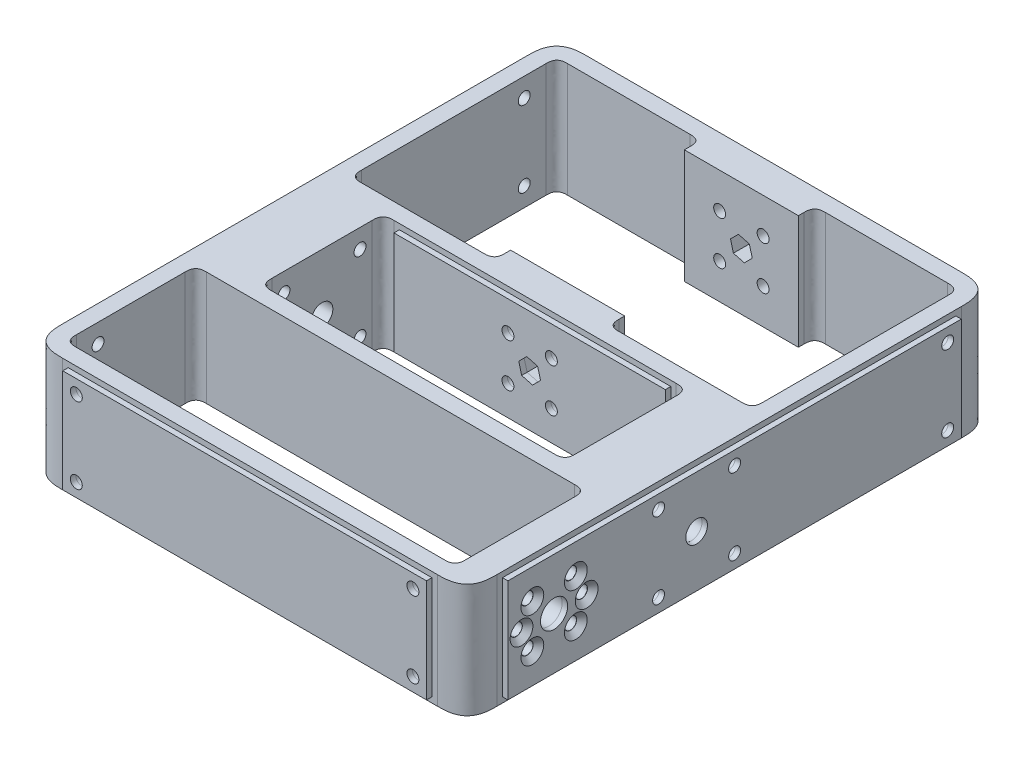
SolidWorks part; units mm, degrees
ref_plane "Front Plane" through (0, 0, 0) normal (0, 0, 1) x (1, 0, 0)
ref_plane "Top Plane" through (0, 0, 0) normal (0, 1, 0) x (1, 0, 0)
ref_plane "Right Plane" through (0, 0, 0) normal (1, 0, 0) x (0, 0, -1)
sketch "Sketch1" plane through (0, 0, 0) normal (0, 1, 0) x (1, 0, 0)
  line L0 (-93.2979, 0) -> (107.2162, 0) construction
  line L1 (-93.2979, -52.5) -> (97.3404, -52.5) construction
  line L2 (-74, -76.5) -> (74, -76.5)
  line L3 (-80, 110.5) -> (80, 110.5)
  line L4 (-80, 110.5) -> (-80, -82.5)
  line L5 (-80, -82.5) -> (80, -82.5)
  line L6 (80, 110.5) -> (80, -82.5)
  line L7 (74, -76.5) -> (74, -28.5)
  line L8 (74, -28.5) -> (-74, -28.5)
  line L9 (-74, -28.5) -> (-74, -76.5)
  line L10 (-74, 104.5) -> (-74, 28.5)
  line L11 (-56, 22.5) -> (56, 22.5)
  line L12 (-56, 22.5) -> (-56, -22.5)
  line L13 (-56, -22.5) -> (56, -22.5)
  line L14 (56, 22.5) -> (56, -22.5)
  line L15 (-74, 28.5) -> (-21, 28.5)
  line L16 (-21, 28.5) -> (-21, 34.5)
  line L17 (-21, 34.5) -> (21, 34.5)
  line L18 (21, 34.5) -> (21, 28.5)
  line L19 (21, 28.5) -> (74, 28.5)
  line L20 (74, 28.5) -> (74, 104.5)
  line L22 (-74, 104.5) -> (-21, 104.5)
  line L23 (-21, 104.5) -> (-21, 98.5)
  line L24 (-21, 98.5) -> (21, 98.5)
  line L25 (21, 98.5) -> (21, 104.5)
  line L26 (21, 104.5) -> (74, 104.5)
  line L27 (-117.8349, 66.5) -> (117.8349, 66.5) construction
  line L28 (0, 98.5) -> (0, 34.5) construction
  point P9 (0, -82.5)
  point P29 (0, -22.5)
  point P31 (0, 98.5)
  point P36 (0, 66.5)
  point P37 (-56, 0)
  dimension "D1" = 52.5
  dimension "D3" = 160
  dimension "D2" = 6
  dimension "D5" = 6
  dimension "D6" = 24
  dimension "D7" = 24
  dimension "D8" = 6
  dimension "D9" = 24
  dimension "D10" = 6
  dimension "D11" = 6
  dimension "D12" = 6
  dimension "D13" = 42
  dimension "D14" = 12
  dimension "D15" = 64
extrude "Boss-Extrude2" add sketch "Sketch1" along normal mid plane 42
fillet "Fillet2" radius 11 4 edges at (80, 0, -110.5) (-80, 0, 82.5) (-80, 0, -110.5) (80, 0, 82.5) curvature continuous yes
sketch "Sketch11" plane through (0, 0, 0) normal (0, 1, 0) x (1, 0, 0)
  line L8 (74, -28.5) -> (-74, -28.5) construction
  line L9 (69.5, -28.5) -> (80, -28.5)
  line L10 (82, 35.9489) -> (82, -108.345) construction
  line L11 (80, -71.5) -> (80, 99.5) construction
  line L12 (69.5, -28.5) -> (69.5, -76.5)
  line L13 (69.5, -76.5) -> (79.5287, -76.5)
  line L14 (80, -28.5) -> (80, -71.5)
  line L15 (-74, -76.5) -> (74, -76.5) construction
  line L16 (79.5287, -76.5) -> (80, -76.5) construction
  line L17 (80, -71.5) -> (80, -76.5) construction
  spline S0 degree 2 poles (-928.7412, -15.3439) (41.6602, -84.362) (71.2832, -82.4484) (72.514, -82.3689) (73.5428, -82.1401) (76.0869, -81.5744) (77.5752, -80.092) (79.066, -78.6071) (79.6366, -76.0586) (79.8669, -75.03) (79.9474, -73.7973) (81.8879, -44.1188) (12.1756, 926.183) knots -4.508241 -4.508241 -4.508241 0.125 0.125 0.25 0.25 0.5 0.5 0.75 0.75 0.875 0.875 5.490692 5.490692 5.490692 only from (69, -82.5) to (80, -71.5) construction
  spline S1 degree 2 poles (79.5287, -76.5) (79.5862, -76.2834) (79.6366, -76.0586) (79.8669, -75.03) (79.9474, -73.7973) (80, -72.9936) (80, -71.5) knots 0.727944 0.727944 0.727944 0.75 0.75 0.875 0.875 1 1 1
  spline S2 degree 2 poles (69, -82.5) (70.484, -82.5) (71.2832, -82.4484) (72.514, -82.3689) (73.5428, -82.1401) (76.0869, -81.5744) (77.5752, -80.092) (78.9345, -78.7381) (79.5287, -76.5) knots 0 0 0 0.125 0.125 0.25 0.25 0.5 0.5 0.727944 0.727944 0.727944 construction
  dimension "D1" = 2
  dimension "D2" = 12.5
extrude "Boss-Extrude5" add sketch "Sketch11" along normal mid plane 42
sketch "Sketch5" plane through (80, 0, 0) normal (1, 0, 0) x (0, 0, -1)
  line L8 (97.5, 19) -> (-69.5, 19)
  line L9 (-69.5, 19) -> (-69.5, -19)
  line L10 (-69.5, -19) -> (97.5, -19)
  line L11 (97.5, -19) -> (97.5, 19)
  line L12 (97.5, 19) -> (-69.5, 19)
  line L14 (-69.5, -19) -> (97.5, -19)
  line L15 (97.5, -19) -> (97.5, 19)
  line L19 (-69.5, 19) -> (-69.5, -19)
  dimension "D1" = 2
extrude "Boss-Extrude3" add sketch "Sketch5" along normal blind 2 separate body
sketch "Sketch9" plane through (-80, 0, 0) normal (-1, 0, 0) x (0, 0, 1)
  line L8 (-97.5, -19) -> (69.5, -19)
  line L9 (69.5, -19) -> (69.5, 19)
  line L10 (69.5, 19) -> (-97.5, 19)
  line L11 (-97.5, 19) -> (-97.5, -19)
  line L12 (-97.5, -19) -> (69.5, -19)
  line L13 (69.5, -19) -> (69.5, 19)
  line L14 (69.5, 19) -> (-97.5, 19)
  line L15 (-97.5, 19) -> (-97.5, -19)
  dimension "D1" = 2
extrude "Boss-Extrude4" add sketch "Sketch9" along normal blind 2 separate body
sketch "Sketch8" plane through (82, 0, 0) normal (1, 0, 0) x (0, 0, -1)
  line L1 (-14, 14) -> (14, 14) construction
  line L2 (-14, 14) -> (-14, -14) construction
  line L3 (-14, -14) -> (14, -14) construction
  line L4 (14, 14) -> (14, -14) construction
  line L5 (-14, 14) -> (14, -14) construction
  line L6 (-14, -14) -> (14, 14) construction
  line L16 (92.5, -14) -> (92.5, 14)
  line L17 (92.5, 14) -> (-64.5, 14)
  line L18 (-64.5, 14) -> (-64.5, -14)
  line L19 (-64.5, -14) -> (92.5, -14)
  line L20 (92.5, -14) -> (92.5, 14) construction
  line L21 (92.5, 14) -> (-64.5, 14) construction
  line L22 (-64.5, 14) -> (-64.5, -14) construction
  line L23 (-64.5, -14) -> (92.5, -14) construction
  circle A0 centre (0, 0) radius 4
  circle A1 centre (-14, 14) radius 2.2
  circle A2 centre (14, 14) radius 2.2
  circle A3 centre (14, -14) radius 2.2
  circle A4 centre (-14, -14) radius 2.2
  circle A9 centre (92.5, -14) radius 2.2
  circle A10 centre (92.5, 14) radius 2.2
  dimension "D1" = 8
  dimension "D2" = 4.4
  dimension "D4" = 5
extrude "Cut-Extrude5" cut sketch "Sketch8" against normal through all
sketch "Sketch6" plane through (0, 0, 0) normal (1, 0, 0) x (0, 0, -1)
  line L0 (-64.5, 0) -> (-40.5, 0) construction
  line L1 (-60.5, 8) -> (-44.5, 8) construction
  line L2 (-60.5, 8) -> (-60.5, -8) construction
  line L3 (-60.5, -8) -> (-44.5, -8) construction
  line L4 (-44.5, 8) -> (-44.5, -8) construction
  line L5 (-60.5, 8) -> (-44.5, -8) construction
  line L6 (-60.5, -8) -> (-44.5, 8) construction
  circle A0 centre (-52.5, 0) radius 5
  circle A1 centre (-60.5, 8) radius 2.2
  circle A2 centre (-44.5, 8) radius 2.2
  circle A3 centre (-44.5, -8) radius 2.2
  circle A4 centre (-60.5, -8) radius 2.2
  circle A5 centre (-64.5, 0) radius 2.2
  circle A6 centre (-40.5, 0) radius 2.2
  dimension "D1" = 52.5
  dimension "D4" = 4.4
  dimension "D5" = 10
  dimension "D2" = 16
  dimension "D3" = 24
extrude "Cut-Extrude3" cut sketch "Sketch6" along normal through all
sketch "Sketch17" plane through (-82, 0, 0) normal (-1, 0, 0) x (0, 0, 1)
  line L8 (-92.5, 14) -> (-92.5, -14)
  line L9 (-92.5, -14) -> (64.5, -14)
  line L10 (64.5, -14) -> (64.5, 14)
  line L11 (64.5, 14) -> (-92.5, 14)
  line L12 (-92.5, 14) -> (-92.5, -14) construction
  line L13 (-92.5, -14) -> (64.5, -14) construction
  line L14 (64.5, -14) -> (64.5, 14) construction
  line L15 (64.5, 14) -> (-92.5, 14) construction
  circle A0 centre (64.5, 14) radius 2.2
  circle A1 centre (64.5, -14) radius 2.2
  dimension "D2" = 4.4
extrude "Cut-Extrude11" cut sketch "Sketch17" against normal up to surface (8 mm away) up to face at (-74, 0, 52.5)
fillet "Fillet4" radius 4 16 edges at (69.5, 0, 28.5) (69.5, 0, 76.5) (-56, 0, -22.5) (-56, 0, 22.5) (56, 0, 22.5) (56, 0, -22.5) (74, 0, -28.5) (-74, 0, -28.5) (-74, 0, 28.5) (74, 0, -104.5) (-74, 0, -104.5) (-74, 0, 76.5) (21, 0, -104.5) (-21, 0, -104.5) (-21, 0, -28.5) (21, 0, -28.5) curvature continuous yes
sketch "Sketch18" plane through (82, 0, 0) normal (1, 0, 0) x (0, 0, -1)
  circle A0 centre (-60.5, -8) radius 2.2 construction
  circle A1 centre (-64.5, 0) radius 2.2 construction
  circle A2 centre (-60.5, 8) radius 2.2 construction
  circle A3 centre (-44.5, 8) radius 2.2 construction
  circle A4 centre (-40.5, 0) radius 2.2 construction
  circle A5 centre (-44.5, -8) radius 2.2 construction
  circle A6 centre (-60.5, -8) radius 2.2
  circle A7 centre (-64.5, 0) radius 2.2
  circle A8 centre (-60.5, 8) radius 2.2
  circle A9 centre (-44.5, 8) radius 2.2
  circle A10 centre (-40.5, 0) radius 2.2
  circle A11 centre (-44.5, -8) radius 2.2
  point P0 (-60.5, -8)
  point P2 (-64.5, 0)
  point P4 (-60.5, 8)
  point P6 (-44.5, 8)
  point P8 (-40.5, 0)
  point P10 (-44.5, -8)
hole_wizard "CSK for M4 Countersunk Flat Head Screw1" positions "Sketch18" profile "Sketch21" countersink size "M4" standard "DIN"
sketch "Sketch21" plane through (82, -8, 60.5) normal (0, 1, 0) x (0, 0, -1)
  line L0 (0, 0) -> (0, 13.8519)
  line L1 (0, 13.8519) -> (2.25, 12.5)
  line L2 (2.25, 12.5) -> (2.25, 1.95)
  line L3 (2.25, 1.95) -> (4.2, 0)
  line L5 (4.2, 0) -> (0, 0)
  line L6 (-2.25, 1.95) -> (-4.2, 0) construction
  line L10 (0, 13.8519) -> (-2.25, 12.5) construction
  line L11 (0, -6.35) -> (0, 107.95) construction
  dimension "Hole Dia." = 4.5
  dimension "Hole Depth" = 12.5
  dimension "Near C'Sink Dia." = 8.4
  dimension "Near C'Sink Angle" = 90
  dimension "Drill Angle" = 118
sketch "Sketch22" plane through (0, 0, -22.5) normal (0, 0, 1) x (1, 0, 0)
  line L8 (50, 19) -> (-50, 19)
  line L9 (-50, 19) -> (-50, -19)
  line L10 (-50, -19) -> (50, -19)
  line L11 (50, -19) -> (50, 19)
  line L12 (50, 19) -> (-50, 19)
  line L13 (-50, 19) -> (-50, -19)
  line L15 (50, -19) -> (50, 19)
  line L17 (-50, -19) -> (50, -19)
  dimension "D1" = 2
extrude "Boss-Extrude6" add sketch "Sketch22" along normal blind 2 separate body
sketch "Sketch29" plane through (0, 0, 22.5) normal (0, 0, -1) x (-1, 0, 0)
  line L8 (-50, -19) -> (50, -19)
  line L9 (50, -19) -> (50, 19)
  line L10 (50, 19) -> (-50, 19)
  line L11 (-50, 19) -> (-50, -19)
  line L12 (-50, -19) -> (50, -19)
  line L13 (50, -19) -> (50, 19)
  line L14 (50, 19) -> (-50, 19)
  line L15 (-50, 19) -> (-50, -19)
  dimension "D1" = 2
extrude "Boss-Extrude9" add sketch "Sketch29" along normal blind 2 separate body
sketch "Sketch23" plane through (0, 0, -110.5) normal (0, 0, -1) x (-1, 0, 0)
  line L8 (67, 19) -> (-67, 19)
  line L9 (-67, 19) -> (-67, -19)
  line L10 (-67, -19) -> (67, -19)
  line L11 (67, -19) -> (67, 19)
  line L12 (67, 19) -> (-67, 19)
  line L13 (-67, 19) -> (-67, -19)
  line L14 (-67, -19) -> (67, -19)
  line L15 (67, -19) -> (67, 19)
  dimension "D1" = 2
extrude "Boss-Extrude7" add sketch "Sketch23" along normal blind 2 separate body
sketch "Sketch24" plane through (0, 0, 0) normal (0, 0, 1) x (1, 0, 0)
  line L0 (2.9394, 2.9394) -> (-2.9394, -2.9394) construction
  line L1 (1.0759, -4.0153) -> (4.0153, -1.0759)
  line L2 (4.0153, -1.0759) -> (2.9394, 2.9394)
  line L3 (2.9394, 2.9394) -> (-1.0759, 4.0153)
  line L4 (-1.0759, 4.0153) -> (-4.0153, 1.0759)
  line L5 (-4.0153, 1.0759) -> (-2.9394, -2.9394)
  line L6 (-2.9394, -2.9394) -> (1.0759, -4.0153)
  line L7 (-8, -8) -> (8, -8) construction
  line L8 (-8, -8) -> (-8, 8) construction
  line L9 (-8, 8) -> (8, 8) construction
  line L10 (8, -8) -> (8, 8) construction
  line L11 (-8, -8) -> (8, 8) construction
  line L12 (-8, 8) -> (8, -8) construction
  circle A0 centre (0, 0) radius 3.6 construction
  circle A1 centre (-8, 8) radius 2.2
  circle A2 centre (8, 8) radius 2.2
  circle A3 centre (8, -8) radius 2.2
  circle A4 centre (-8, -8) radius 2.2
  dimension "D3" = 4.4
  dimension "D1" = 7.2
  dimension "D2" = 16
extrude "Cut-Extrude12" cut sketch "Sketch24" against normal through all
sketch "Sketch27" plane through (0, 0, 82.5) normal (0, 0, 1) x (1, 0, 0)
  line L8 (-67, -19) -> (67, -19)
  line L9 (67, -19) -> (67, 19)
  line L10 (67, 19) -> (-67, 19)
  line L11 (-67, 19) -> (-67, -19)
  line L12 (-67, -19) -> (67, -19)
  line L13 (67, -19) -> (67, 19)
  line L14 (67, 19) -> (-67, 19)
  line L15 (-67, 19) -> (-67, -19)
  dimension "D1" = 2
extrude "Boss-Extrude8" add sketch "Sketch27" along normal blind 2 separate body
sketch "Sketch28" plane through (0, 0, 84.5) normal (0, 0, 1) x (1, 0, 0)
  line L8 (-62, 14) -> (-62, -14)
  line L9 (-62, -14) -> (62, -14)
  line L10 (62, -14) -> (62, 14)
  line L11 (62, 14) -> (-62, 14)
  line L12 (-62, 14) -> (-62, -14) construction
  line L13 (-62, -14) -> (62, -14) construction
  line L14 (62, -14) -> (62, 14) construction
  line L15 (62, 14) -> (-62, 14) construction
  circle A0 centre (-62, 14) radius 2.2
  circle A1 centre (-62, -14) radius 2.2
  circle A2 centre (62, -14) radius 2.2
  circle A3 centre (62, 14) radius 2.2
  dimension "D2" = 4.4
extrude "Cut-Extrude14" cut sketch "Sketch28" against normal up to surface (8 mm away) up to face at (-36.125, 0, 76.5)
equation "\"motor_center_distance_to_axle\"= 52.5mm"
equation "\"width\"= 160mm"
equation "\"height\"= 42mm"
equation "\"wall_thickness\"= 6mm"
equation "\"aluminum_thickness\"= 2.0mm"
equation "\"D1@Sketch1\"=\"motor_center_distance_to_axle\""
equation "\"D3@Sketch1\"=\"width\""
equation "\"depth\"= 200mm"
equation "\"D2@Sketch1\"=\"wall_thickness\""
equation "\"D5@Sketch1\"=\"wall_thickness\""
equation "\"D8@Sketch1\"=\"wall_thickness\""
equation "\"D10@Sketch1\"=\"wall_thickness\""
equation "\"D11@Sketch1\"=\"wall_thickness\""
equation "\"D12@Sketch1\"=\"wall_thickness\""
equation "\"D13@Sketch1\"=\"height\""
equation "\"spine_center_distance_to_axle\"= 64mm"
equation "\"spine_width\"= 42mm"
equation "\"D15@Sketch1\"=\"spine_width\"+10mm+12mm"
equation "\"D1@Boss-Extrude2\"=\"height\""
equation "\"D1@Boss-Extrude3\"=\"aluminum_thickness\""
equation "\"D1@Sketch6\"=\"motor_center_distance_to_axle\""
equation "\"plate_hole_inset\"= 5mm"
equation "\"D1@Boss-Extrude4\"=\"aluminum_thickness\""
equation "\"D4@Sketch8\"=\"plate_hole_inset\""
equation "\"D1@Boss-Extrude5\"=\"height\""
equation "\"D1@Sketch11\"=\"aluminum_thickness\""
equation "\"D1@Sketch17\"=\"plate_hole_inset\""
equation "\"D1@Boss-Extrude7\"=\"aluminum_thickness\""
equation "\"D1@Boss-Extrude8\"=\"aluminum_thickness\""
equation "\"D1@Sketch28\"=\"plate_hole_inset\""
equation "\"D1@Boss-Extrude6\"=\"aluminum_thickness\""
equation "\"D1@Boss-Extrude9\"=\"aluminum_thickness\""
equation "\"spine_cavity_depth\"= 80mm"
equation "\"fillet_radius\"= 10mm"
